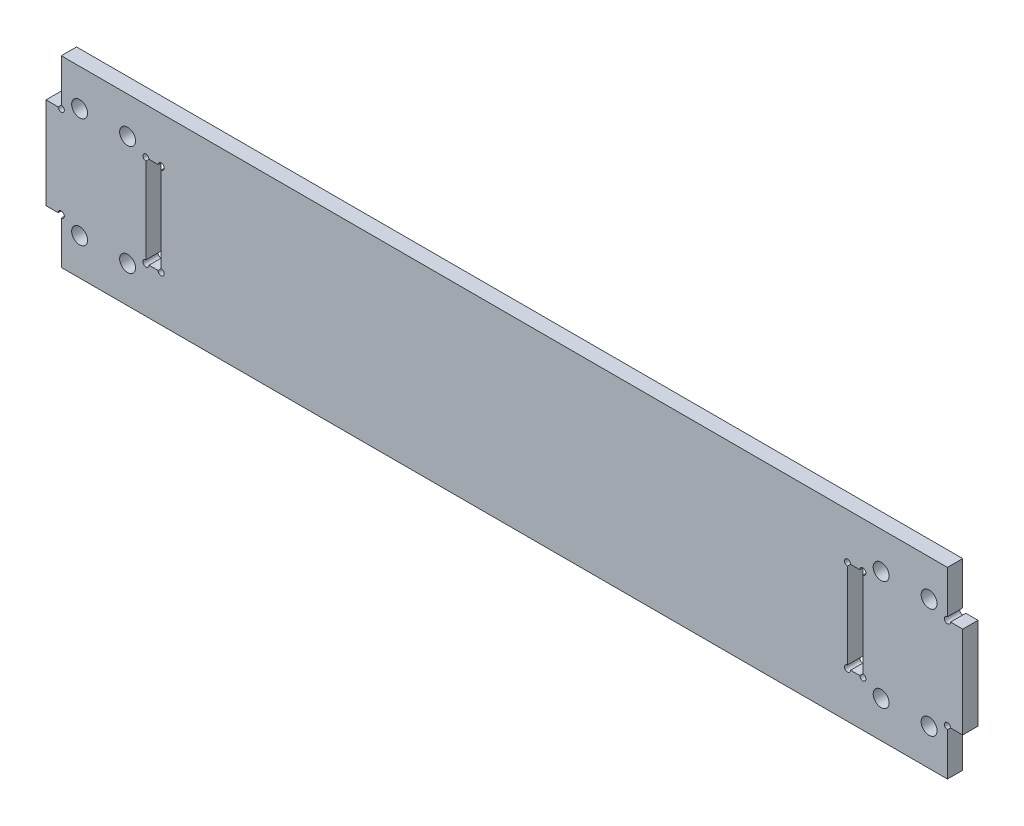
SolidWorks part; units mm, degrees
ref_plane "前视基准面" through (0, 0, 0) normal (0, 0, 1) x (1, 0, 0)
ref_plane "上视基准面" through (0, 0, 0) normal (0, 1, 0) x (1, 0, 0)
ref_plane "右视基准面" through (0, 0, 0) normal (1, 0, 0) x (0, 0, -1)
other "Configuration Table"
sketch "草图1" plane through (0, 0, 0) normal (0, 0, 1) x (1, 0, 0)
  line L1 (0, 0) -> (290, 0)
  line L2 (0, 0) -> (0, -60)
  line L3 (0, -60) -> (290, -60)
  line L4 (290, 0) -> (290, -60)
  dimension "D1" = 60
  dimension "D2" = 290
extrude "凸台-拉伸1" add sketch "草图1" along normal blind 5
sketch "草图2" plane through (0, 0, 5) normal (0, 0, 1) x (1, 0, 0)
  line L0 (145, 0) -> (145, -60)
  line L1 (0, -15) -> (-5, -15)
  line L2 (0, -15) -> (0, -45)
  line L3 (0, -45) -> (-5, -45)
  line L4 (0, 0) -> (0, -60)
  line L5 (0, -60) -> (290, -60)
  line L6 (290, -60) -> (290, 0)
  line L7 (290, 0) -> (0, 0)
  line L8 (0, 0) -> (0, -60)
  line L9 (0, -60) -> (290, -60)
  line L10 (290, -60) -> (290, 0)
  line L11 (290, 0) -> (0, 0)
  line L12 (-5, -15) -> (-5, -45)
  line L13 (290, -45) -> (295, -45)
  line L14 (295, -15) -> (295, -45)
  line L15 (290, -15) -> (295, -15)
  line L16 (290, -15) -> (290, -45)
  dimension "D2" = 30
  dimension "D3" = 15
  dimension "D4" = 5
  dimension "D1" = 0
extrude "凸台-拉伸2" add sketch "草图2" against normal blind 5 contours L15 L10 L13 L14 | L2 L3 L12 L1 region at (292.5, -30, 5)
sketch "草图3" plane through (0, 0, 0) normal (0, 0, -1) x (-1, 0, 0)
  line L12 (0, -15) -> (0, 0)
  line L13 (0, 0) -> (-290, 0)
  line L14 (-290, 0) -> (-290, -15)
  line L15 (-290, -15) -> (-295, -15)
  line L16 (-295, -15) -> (-295, -45)
  line L17 (-295, -45) -> (-290, -45)
  line L18 (-290, -45) -> (-290, -60)
  line L19 (-290, -60) -> (0, -60)
  line L20 (0, -60) -> (0, -45)
  line L21 (0, -45) -> (5, -45)
  line L22 (5, -45) -> (5, -15)
  line L23 (5, -15) -> (0, -15)
  line L24 (0, -15) -> (0, 0)
  line L25 (0, 0) -> (-290, 0)
  line L26 (-290, 0) -> (-290, -15)
  line L27 (-290, -15) -> (-295, -15)
  line L28 (-295, -15) -> (-295, -45)
  line L29 (-295, -45) -> (-290, -45)
  line L30 (-290, -45) -> (-290, -60)
  line L31 (-290, -60) -> (0, -60)
  line L32 (0, -60) -> (0, -45)
  line L33 (0, -45) -> (5, -45)
  line L34 (5, -45) -> (5, -15)
  line L35 (5, -15) -> (0, -15)
  circle A0 centre (-290, -15) radius 1
  circle A1 centre (-290, -45) radius 1
  circle A2 centre (0, -15) radius 1
  circle A3 centre (0, -45) radius 1
  line M13 (0, -15) -> (0, 0)
  line M16 (-290, -15) -> (-295, -15)
  line M19 (-290, -45) -> (-290, -60)
  line M22 (0, -45) -> (5, -45)
  dimension "D2" = 2
  dimension "D3" = 2
  dimension "D4" = 2
  dimension "D5" = 2
  dimension "D1" = 0
extrude "切除-拉伸1" cut sketch "草图3" against normal blind 5 contours A0 L26 M16 | A1 L29 M19 | A2 L35 M13 | A3 L32 M22 region at (0.1415, -15.1415, 0) region at (289.8585, -15.1415, 0) region at (0.1415, -44.8585, 0) region at (289.8585, -44.8585, 0)
sketch "草图4" plane through (0, 0, 0) normal (0, 0, -1) x (-1, 0, 0)
  line L0 (-145, 0) -> (-145, -60) construction
  line L1 (-262.3, -15) -> (-257.3, -15)
  line L2 (-262.3, -15) -> (-262.3, -45)
  line L3 (-262.3, -45) -> (-257.3, -45)
  line L4 (-257.3, -15) -> (-257.3, -45)
  line L5 (-27.7, -45) -> (-32.7, -45)
  line L6 (-32.7, -15) -> (-32.7, -45)
  line L7 (-27.7, -15) -> (-32.7, -15)
  line L8 (-27.7, -15) -> (-27.7, -45)
  line L12 (-295, -45) -> (-291, -45)
  line L13 (-290, -46) -> (-290, -60)
  line L14 (-290, -60) -> (0, -60)
  line L15 (0, -60) -> (0, -46)
  line L16 (1, -45) -> (5, -45)
  line L17 (5, -45) -> (5, -15)
  line L18 (5, -15) -> (1, -15)
  line L19 (0, -14) -> (0, 0)
  line L20 (0, 0) -> (-290, 0)
  line L21 (-290, 0) -> (-290, -14)
  line L22 (-291, -15) -> (-295, -15)
  line L23 (-295, -15) -> (-295, -45)
  line L24 (-295, -45) -> (-291, -45)
  line L25 (-290, -46) -> (-290, -60)
  line L26 (-290, -60) -> (0, -60)
  line L27 (0, -60) -> (0, -46)
  line L28 (1, -45) -> (5, -45)
  line L29 (5, -45) -> (5, -15)
  line L30 (5, -15) -> (1, -15)
  line L31 (0, -14) -> (0, 0)
  line L32 (0, 0) -> (-290, 0)
  line L33 (-290, 0) -> (-290, -14)
  line L34 (-291, -15) -> (-295, -15)
  line L35 (-295, -15) -> (-295, -45)
  circle A0 centre (-257.3, -15) radius 1
  circle A1 centre (-262.3, -15) radius 1
  circle A2 centre (-262.3, -45) radius 1
  circle A3 centre (-257.3, -45) radius 1
  arc A4 (-290, -46) -> (-291, -45) centre (-290, -45) ccw
  arc A5 (1, -45) -> (0, -46) centre (0, -45) ccw
  arc A6 (0, -14) -> (1, -15) centre (0, -15) ccw
  arc A7 (-291, -15) -> (-290, -14) centre (-290, -15) ccw
  arc A8 (-290, -46) -> (-291, -45) centre (-290, -45) ccw
  arc A9 (1, -45) -> (0, -46) centre (0, -45) ccw
  arc A10 (0, -14) -> (1, -15) centre (0, -15) ccw
  arc A11 (-291, -15) -> (-290, -14) centre (-290, -15) ccw
  circle A12 centre (-32.7, -15) radius 1
  circle A13 centre (-27.7, -15) radius 1
  circle A14 centre (-32.7, -45) radius 1
  circle A15 centre (-27.7, -45) radius 1
  dimension "D6" = 2
  dimension "D7" = 2
  dimension "D8" = 2
  dimension "D9" = 2
  dimension "D10" = 2
  dimension "D11" = 2
  dimension "D12" = 2
  dimension "D13" = 2
  dimension "D2" = 27.7
  dimension "D3" = 5
  dimension "D4" = 15
  dimension "D5" = 15
  dimension "D1" = 0
extrude "切除-拉伸2" cut sketch "草图4" against normal blind 5 contours L1 A1 L2 | L2 A1 L1 | A3 L4 A0 L1 A1 L2 A2 L3 | L1 A0 L4 | L4 A0 L1 | L3 A2 L2 | L2 A2 L3 | L4 A3 L3 | L3 A3 L4 | L7 A12 L6 | L6 A12 L7 | A15 L8 A13 L7 A12 L6 A14 L5 | L7 A13 L8 | L8 A13 L7 | L6 A14 L5 | L5 A14 L6 | L5 A15 L8 | L8 A15 L5 region at (262.4415, -14.8585, 0) region at (261.8756, -15.4244, 0) region at (259.8, -30, 0) region at (257.1585, -14.8585, 0) region at (257.7244, -15.4244, 0) region at (261.8756, -44.5756, 0) region at (262.4415, -45.1415, 0) region at (257.1585, -45.1415, 0) region at (257.7244, -44.5756, 0) region at (32.8415, -45.1415, 0) region at (30.2, -30, 0) region at (32.2756, -44.5756, 0) region at (28.1244, -44.5756, 0) region at (27.5585, -45.1415, 0) region at (32.8415, -14.8585, 0) region at (32.2756, -15.4244, 0) region at (28.1244, -15.4244, 0) region at (27.5585, -14.8585, 0)
sketch "草图5" plane through (0, 0, 5) normal (0, 0, 1) x (1, 0, 0)
  line L0 (27.7, -16) -> (27.7, -44) construction
  line L1 (-5, -30) -> (295, -30)
  line L2 (145, 0) -> (145, -60)
  line L12 (291, -45) -> (295, -45)
  line L13 (295, -45) -> (295, -15)
  line L14 (295, -15) -> (291, -15)
  line L15 (290, -14) -> (290, 0)
  line L16 (290, 0) -> (0, 0)
  line L17 (0, 0) -> (0, -14)
  line L18 (-1, -15) -> (-5, -15)
  line L19 (-5, -15) -> (-5, -45)
  line L20 (-5, -45) -> (-1, -45)
  line L21 (0, -46) -> (0, -60)
  line L22 (0, -60) -> (290, -60)
  line L23 (290, -60) -> (290, -46)
  line L24 (291, -45) -> (295, -45)
  line L25 (295, -45) -> (295, -15)
  line L26 (295, -15) -> (291, -15)
  line L27 (290, -14) -> (290, 0)
  line L28 (290, 0) -> (0, 0)
  line L29 (0, 0) -> (0, -14)
  line L30 (-1, -15) -> (-5, -15)
  line L31 (-5, -15) -> (-5, -45)
  line L32 (-5, -45) -> (-1, -45)
  line L33 (0, -46) -> (0, -60)
  line L34 (0, -60) -> (290, -60)
  line L35 (290, -60) -> (290, -46)
  circle A0 centre (6, -48) radius 2.6
  circle A1 centre (21.7, -48) radius 2.6
  circle A2 centre (21.7, -12) radius 2.6
  circle A3 centre (6, -12) radius 2.6
  arc A4 (291, -45) -> (290, -46) centre (290, -45) ccw
  arc A5 (290, -14) -> (291, -15) centre (290, -15) ccw
  arc A6 (-1, -15) -> (0, -14) centre (0, -15) ccw
  arc A7 (0, -46) -> (-1, -45) centre (0, -45) ccw
  arc A8 (291, -45) -> (290, -46) centre (290, -45) ccw
  arc A9 (290, -14) -> (291, -15) centre (290, -15) ccw
  arc A10 (-1, -15) -> (0, -14) centre (0, -15) ccw
  arc A11 (0, -46) -> (-1, -45) centre (0, -45) ccw
  circle A12 centre (268.3, -48) radius 2.6
  circle A13 centre (284, -48) radius 2.6
  circle A14 centre (268.3, -12) radius 2.6
  circle A15 centre (284, -12) radius 2.6
  dimension "D2" = 12
  dimension "D3" = 12
  dimension "D4" = 5.2
  dimension "D5" = 5.2
  dimension "D6" = 6
  dimension "D7" = 6
  dimension "D1" = 0
extrude "切除-拉伸3" cut sketch "草图5" against normal through all contours A3 | A2 | A0 | A1 | A14 | A15 | A12 | A13 region at (6, -48, 5) region at (21.7, -48, 5) region at (21.7, -12, 5) region at (6, -12, 5) region at (268.3, -48, 5) region at (284, -48, 5) region at (268.3, -12, 5) region at (284, -12, 5)
